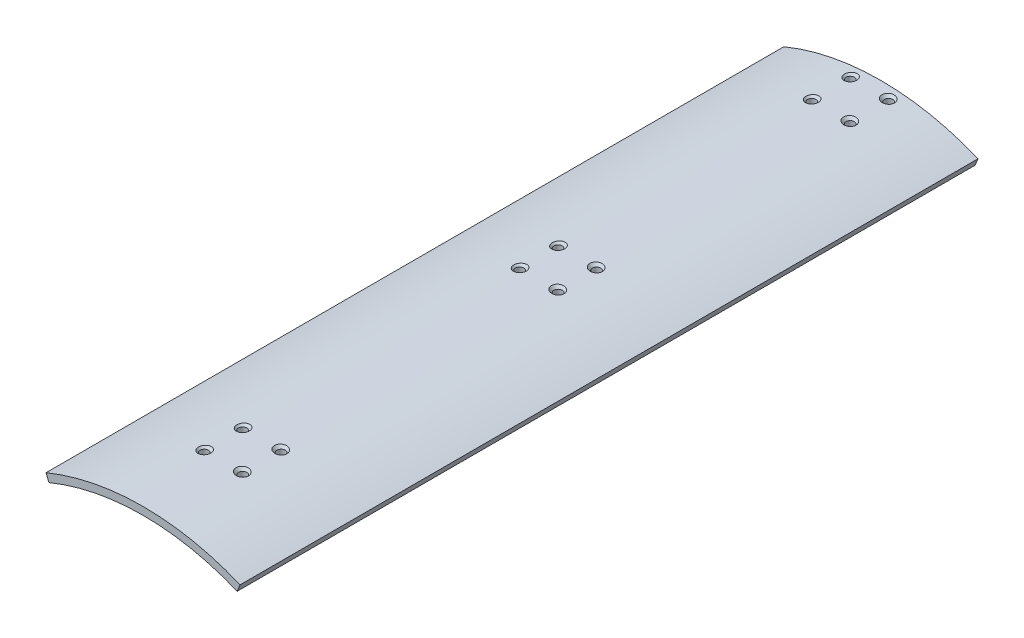
SolidWorks part; units mm, degrees
ref_plane "Front Plane" through (0, 0, 0) normal (0, 0, 1) x (1, 0, 0)
ref_plane "Top Plane" through (0, 0, 0) normal (0, 1, 0) x (1, 0, 0)
ref_plane "Right Plane" through (0, 0, 0) normal (1, 0, 0) x (0, 0, -1)
sketch "Sketch1" plane through (0, 0, 0) normal (0, 0, 1) x (1, 0, 0)
  line L0 (-40.0957, 96.7995) -> (-38.8806, 93.8662)
  line L1 (0, 0) -> (0, 104.775) construction
  line L2 (40.0957, 96.7995) -> (38.8806, 93.8662)
  arc A0 (-40.0957, 96.7995) -> (40.0957, 96.7995) centre (0, 0) cw
  arc A2 (-38.8806, 93.8662) -> (38.8806, 93.8662) centre (0, 0) cw
  dimension "D1" = 101.6
  dimension "D2" = 104.775
  dimension "D3" = 45
extrude "Boss-Extrude1" add sketch "Sketch1" along normal blind 152.4 and the other way blind 152.4
sketch "Sketch2" plane through (0, 0, 152.4) normal (0, 0, 1) x (1, 0, 0)
  arc A0 (40.0957, 96.7995) -> (-40.0957, 96.7995) centre (0, 0) ccw construction
  point P0 (0, 104.775)
ref_plane "Plane1" through (0, 104.775, 0) normal (0, 1, 0) x (1, 0, 0)
sketch "Sketch3" plane through (0, 104.775, 0) normal (0, 1, 0) x (1, 0, 0)
  line L0 (40.0957, 152.4) -> (-40.0957, 152.4) construction
  line L1 (0, -5.9999) -> (0, 5.9999) construction
  circle A0 centre (7.9375, 26.9875) radius 2.8448
  circle A1 centre (7.9375, 11.1125) radius 2.8448
  circle A2 centre (-7.9375, 26.9875) radius 2.8448
  circle A3 centre (-7.9375, 11.1125) radius 2.8448
  circle A4 centre (7.9375, -103.3145) radius 2.8448
  circle A5 centre (7.9375, -119.1895) radius 2.8448
  circle A6 centre (-7.9375, -119.1895) radius 2.8448
  circle A7 centre (-7.9375, -103.3145) radius 2.8448
  circle A8 centre (7.9375, 147.6375) radius 2.8448
  circle A9 centre (7.9375, 131.7625) radius 2.8448
  circle A10 centre (-7.9375, 131.7625) radius 2.8448
  circle A11 centre (-7.9375, 147.6375) radius 2.8448
  dimension "D1" = 125.4125
  dimension "D2" = 15.875
  dimension "D5" = 7.9375
  dimension "D3" = 15.875
  dimension "D4" = 7.9375
  dimension "D6" = 2
  dimension "D7" = 2
ref_plane "Plane2" through (0, 104.775, 0) normal (0, 1, 0) x (1, 0, 0)
sketch "Sketch9" plane through (0, 104.775, 0) normal (0, 1, 0) x (1, 0, 0)
  line L0 (40.0957, 152.4) -> (-40.0957, 152.4) construction
  circle A0 centre (7.9375, 26.9875) radius 2.8448
  circle A1 centre (-7.9375, 26.9875) radius 2.8448
  circle A2 centre (7.9375, 11.1125) radius 2.8448
  circle A3 centre (-7.9375, 11.1125) radius 2.8448
  circle A4 centre (7.9375, -119.1895) radius 2.8448
  circle A5 centre (-7.9375, -119.1895) radius 2.8448
  circle A6 centre (-7.9375, -103.3145) radius 2.8448
  circle A7 centre (7.9375, -103.3145) radius 2.8448
  circle A8 centre (7.9375, 131.7625) radius 2.8448
  circle A9 centre (-7.9375, 131.7625) radius 2.8448
  circle A10 centre (-7.9375, 147.6375) radius 2.8448
  circle A11 centre (7.9375, 147.6375) radius 2.8448
  dimension "D1" = 125.4125
  dimension "D3" = 15.875
  dimension "D5" = 2
  dimension "D2" = 15.875
  dimension "D4" = 15.875
  dimension "D7" = 7.9375
  dimension "D6" = 2
hole_wizard "CSK for #4 Flat Head Machine Screw (100)2" positions "Sketch11" profile "Sketch10" countersink size "#4" standard "ANSI Inch" end condition through all
sketch "Sketch11" plane through (0, 104.775, 0) normal (0, 1, 0) x (1, 0, 0)
  point P0 (7.9375, 147.6375)
  point P3 (7.9375, 131.7625)
  point P6 (-7.9375, 131.7625)
  point P9 (-7.9375, 147.6375)
  point P12 (7.9375, 26.9875)
  point P15 (7.9375, 11.1125)
  point P18 (-7.9375, 11.1125)
  point P21 (-7.9375, 26.9875)
  point P24 (7.9375, -103.3145)
  point P27 (7.9375, -119.1895)
  point P30 (-7.9375, -119.1895)
  point P33 (-7.9375, -103.3145)
sketch "Sketch10" plane through (7.9375, 104.775, -147.6375) normal (1, 0, 0) x (0, 0, 1)
  line L0 (0, 0) -> (0, 10.9088)
  line L1 (0, 10.9088) -> (1.7272, 10.9088)
  line L2 (1.7272, 10.9088) -> (1.7272, 1.3003)
  line L3 (1.7272, 1.3003) -> (2.8575, 0)
  line L5 (2.8575, 0) -> (0, 0)
  line L6 (-1.7272, 1.3003) -> (-2.8575, 0) construction
  line L11 (0, -6.35) -> (0, 107.95) construction
  dimension "Thru Hole Dia." = 3.4544
  dimension "Thru Hole Depth" = 10.9088
  dimension "Near C'Sink Dia." = 5.715
  dimension "Near C'Sink Angle" = 82
